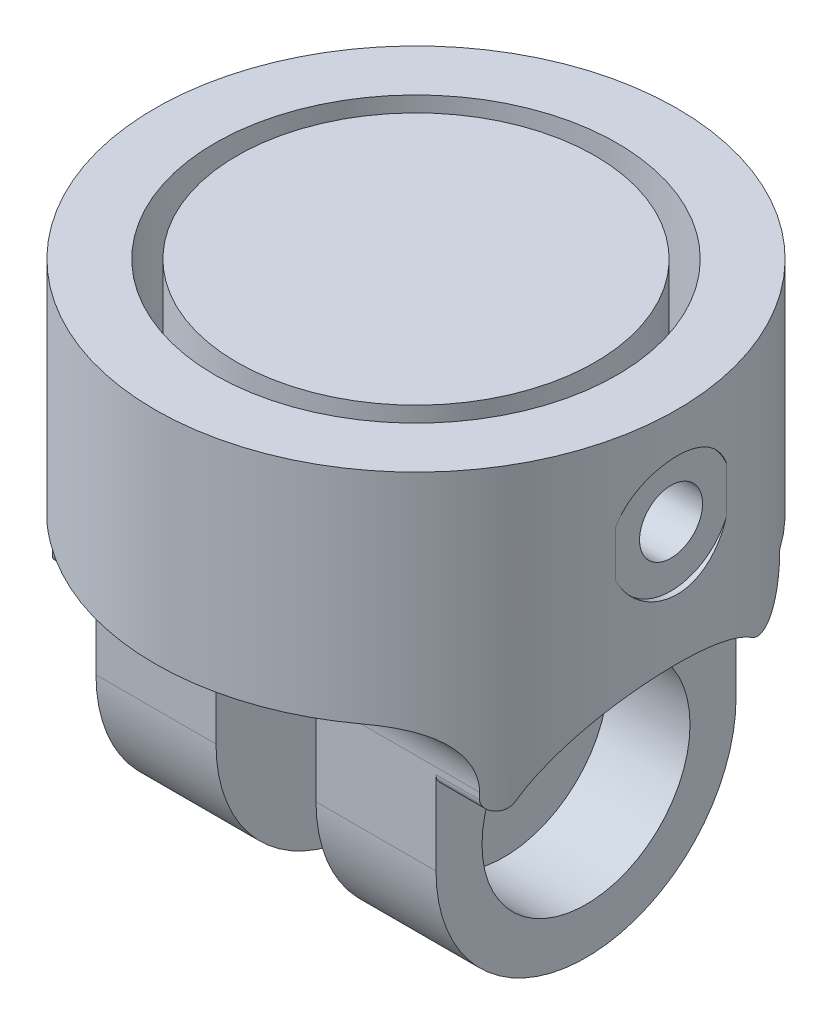
SolidWorks part; units mm, degrees
material "PLA Black"
ref_plane "Front" through (0, 0, 0) normal (0, 0, 1) x (1, 0, 0)
ref_plane "Top" through (0, 0, 0) normal (0, 1, 0) x (1, 0, 0)
ref_plane "Right" through (0, 0, 0) normal (1, 0, 0) x (0, 0, -1)
sketch "Sketch1" plane through (0, 0, 0) normal (0, 1, 0) x (1, 0, 0)
  line L0 (0, 8.95) -> (0, 10.05) construction
  circle A0 centre (0, 0) radius 10.05
  circle A1 centre (0, 0) radius 13.05
  circle A2 centre (0, 0) radius 9.5 construction
  circle A4 centre (0, 0) radius 8.95
  point P11 (0, 9.5)
  dimension "D1" = 1.1
  dimension "D2" = 3
  dimension "D3" = 19
extrude "Boss-Extrude1" add sketch "Sketch1" along normal blind 10 contours A1 A0 | A4 region at (-12.6809, 0, 0) region at (0, 0, 0)
sketch "Sketch3" plane through (0, 0, 0) normal (0, -1, 0) x (1, 0, 0)
  circle A2 centre (0, 0) radius 13.05 construction
  circle A3 centre (0, 0) radius 13.05
extrude "Boss-Extrude2" add sketch "Sketch3" along normal blind 1
sketch "Sketch4" plane through (0, -1, 0) normal (0, -1, 0) x (1, 0, 0)
  line L0 (0, 17.8908) -> (0, -17.0763) construction
  line L1 (2.5, 7.5) -> (8.5, 7.5)
  line L2 (2.5, 7.5) -> (2.5, -7.5)
  line L3 (2.5, -7.5) -> (8.5, -7.5)
  line L4 (8.5, 7.5) -> (8.5, -7.5)
  line L5 (-8.5, 7.5) -> (-8.5, -7.5)
  line L6 (-2.5, -7.5) -> (-8.5, -7.5)
  line L7 (-2.5, 7.5) -> (-2.5, -7.5)
  line L8 (-2.5, 7.5) -> (-8.5, 7.5)
  line L9 (16.8049, 0) -> (-19.8998, 0) construction
  dimension "D1" = 6
  dimension "D2" = 5
  dimension "D3" = 15
extrude "Boss-Extrude3" add sketch "Sketch4" along normal blind 15
sketch "Sketch5" plane through (8.5, 0, 0) normal (1, 0, 0) x (0, 0, -1)
  line L0 (-7.5, -16) -> (-7.5, -1) construction
  line L1 (7.5, -16) -> (7.5, -1) construction
  line L2 (7.5, -8.5) -> (7.5, -17.1619)
  line L3 (7.5, -17.1619) -> (-7.5, -17.1619)
  line L4 (-7.5, -17.1619) -> (-7.5, -8.5)
  arc A0 (-7.5, -8.5) -> (7.5, -8.5) centre (0, -8.5) ccw
  circle A1 centre (0, -8.5) radius 1.55
  dimension "D1" = 3.1
extrude "Cut-Extrude1" cut sketch "Sketch5" against normal through all both and the other way through all
sketch "Sketch6" plane through (8.5, 0, 0) normal (1, 0, 0) x (0, 0, -1)
  circle A0 centre (0, -8.5) radius 5.2
  dimension "D1" = 10.4
extrude "Cut-Extrude2" cut sketch "Sketch6" against normal blind 4.1
mirror "Mirror1" about plane through (0, 0, 0) normal (1, 0, 0) of "Cut-Extrude2"
ref_plane "Plane9" through (1.335, 0, 0) normal (1, 0, 0) x (0, 0, -1)
sketch "Sketch7" plane through (1.335, 0, 0) normal (1, 0, 0) x (0, 0, -1)
  line L0 (3.555, -8.5) -> (3.555, -1) construction
  line L1 (7.5, -1) -> (-7.5, -1) construction
  line L2 (3.4474, -7.632) -> (1.7775, -1) construction
  line L3 (3.1303, -6.8149) -> (0, -1) construction
  line L4 (1.7775, -0.6757) -> (1.7775, -1.4422) construction
  line L5 (2.6911, -6.1771) -> (-1.7775, -1) construction
  line L6 (2.2506, -5.7481) -> (-3.555, -1) construction
  line L8 (0, -1.6788) -> (0, 0) construction
  line L9 (-8.4824, -8.5) -> (8.712, -8.5) construction
  line L10 (1.8766, -5.4807) -> (-5.3325, -1) construction
  line L11 (-3.555, -0.3587) -> (-3.555, -1.6788) construction
  circle A0 centre (0, -8.5) radius 3.555 construction
  dimension "D1" = 7.11
  dimension "D2" = 31.862
  dimension "D3" = 7.5
ref_plane "Plane1" through (1.335, -1, -3.555) normal (0, 1, 0) x (1, 0, 0)
ref_plane "Plane2" through (1.335, -1, -1.7775) normal (0, 0.9697, 0.2442) x (1, 0, 0)
ref_plane "Plane3" through (1.335, -1, 0) normal (0, 0.8805, 0.474) x (1, 0, 0)
ref_plane "Plane5" through (1.335, -1, 1.7775) normal (0, 0.757, 0.6534) x (1, 0, 0)
ref_plane "Plane6" through (1.335, -1, 3.555) normal (0, 0.6331, 0.7741) x (1, 0, 0)
ref_plane "Plane7" through (1.335, -1, 5.3325) normal (0, 0.5279, 0.8493) x (1, 0, 0)
sketch "Sketch8" plane through (1.335, -1, -3.555) normal (0, 1, 0) x (1, 0, 0)
  circle A0 centre (0, 0) radius 0.4895
  dimension "D1" = 0.979
extrude "Cut-Extrude5" cut sketch "Sketch8" along normal blind 5.5 and the other way through all
sketch "Sketch9" plane through (1.335, -1, -1.7775) normal (0, 0.9697, 0.2442) x (1, 0, 0)
  circle A0 centre (0, 0) radius 0.4895
  dimension "D1" = 0.979
extrude "Cut-Extrude3" cut sketch "Sketch9" along normal blind 5.5
sketch "Sketch10" plane through (1.335, -1, 0) normal (0, 0.8805, 0.474) x (1, 0, 0)
  circle A0 centre (0, 0) radius 0.4895
  dimension "D1" = 0.979
sketch "Sketch11" plane through (1.335, -1, 1.7775) normal (0, 0.757, 0.6534) x (1, 0, 0)
  circle A0 centre (0, 0) radius 0.4895
  dimension "D1" = 0.979
sketch "Sketch12" plane through (1.335, -1, 3.555) normal (0, 0.6331, 0.7741) x (1, 0, 0)
  circle A0 centre (0, 0) radius 0.4895
  dimension "D1" = 0.979
sketch "Sketch14" plane through (1.335, -1, 5.3325) normal (0, 0.5279, 0.8493) x (1, 0, 0)
  circle A0 centre (0, 0) radius 0.4895
  dimension "D1" = 0.979
extrude "Cut-Extrude6" cut sketch "Sketch10" along normal blind 5.5 and the other way through all
extrude "Cut-Extrude7" cut sketch "Sketch11" along normal blind 5.5 and the other way through all contours A0
extrude "Cut-Extrude8" cut sketch "Sketch12" along normal blind 5.5 and the other way through all contours A0
extrude "Cut-Extrude9" cut sketch "Sketch14" along normal blind 5.5 and the other way through all contours A0
ref_plane "Plane8" through (13.05, 0, 0) normal (1, 0, 0) x (0, 0, -1)
hole_wizard "Tap Drill for M3 Helicoil1" positions "Sketch17" profile "Sketch18" hole size "M3x0.5" standard "DIN"
sketch "Sketch17" plane through (13.05, 0, 0) normal (1, 0, 0) x (0, 0, -1)
  line L0 (-22.2973, 5) -> (18.0703, 5) construction
  line L4 (0, 12.2732) -> (0, -5.3405) construction
  line L6 (-7.5, -8.5) -> (-7.5, -1) construction
  line L7 (7.5, -8.5) -> (7.5, -1) construction
  line L8 (13.05, 10) -> (-13.05, 10) construction
  line L9 (10.05, 0) -> (-10.05, 0) construction
  point P0 (0, 5)
sketch "Sketch18" plane through (13.05, 5, 0) normal (0, 1, 0) x (0, 0, -1)
  line L0 (0, 0) -> (0, 6.9464)
  line L1 (0, 6.9464) -> (1.575, 6)
  line L2 (1.575, 6) -> (1.575, 0)
  line L5 (1.575, 0) -> (0, 0)
  line L10 (0, 6.9464) -> (-1.575, 6) construction
  line L11 (0, -6.35) -> (0, 107.95) construction
  dimension "Hole Dia." = 3.15
  dimension "Hole Depth" = 6
  dimension "Drill Angle" = 118
sketch "Sketch20" plane through (13.05, 0, 0) normal (1, 0, 0) x (0, 0, -1)
  circle A0 centre (0, 5) radius 3
  dimension "D1" = 6
extrude "Cut-Extrude10" cut sketch "Sketch20" against normal blind 0.3
sketch "Sketch21" plane through (8.5, 0, 0) normal (1, 0, 0) x (0, 0, -1)
  line L0 (7.5, -1) -> (-7.5, -1) construction
  line L1 (7.5, -0.1252) -> (7.5, -1.1767)
  line L2 (0.9244, -19.0662) -> (-4.8209, -14.2453) construction
  line L3 (0, 5.2718) -> (0, -9.2894) construction
  line L4 (0, 10) -> (0, -1) construction
  line L5 (-7.5, -0.1252) -> (-7.5, -4.3226)
  line L6 (7.5, -0.1252) -> (-7.5, -0.1252)
  line L7 (-7.5, -8.5) -> (-7.5, -1) construction
  line L8 (7.5, -8.5) -> (7.5, -1) construction
  line L9 (0, -1) -> (9.4693, -4.4465) construction
  line L10 (0, -1) -> (1.6171, -0.0664) construction
  line L11 (4.6128, -2.5863) -> (7.5, -1.1767) construction
  line L12 (10.5662, -7.5756) -> (4.8209, -2.7547) construction
  line L13 (-4.8209, -14.2453) -> (4.8209, -2.7547) construction
  line L14 (10.5662, -7.5756) -> (0.9244, -19.0662) construction
  arc A0 (-6.4204, -4.6233) -> (4.6128, -2.5863) centre (0, -8.5) cw
  arc A1 (-6.4204, -4.6233) -> (-7.5, -4.3226) centre (-6.9183, -4.3226) cw
  arc A2 (7.5, -1.1767) -> (4.6128, -2.5863) centre (5.7123, -1.1767) cw
  circle A3 centre (0, -8.5) radius 1.55 construction
  arc A4 (-4.8209, -14.2453) -> (4.8209, -2.7547) centre (0, -8.5) cw construction
  dimension "D1" = 30
  dimension "D3" = 7.5
  dimension "D2" = 50
  dimension "D4" = 15
extrude "Boss-Extrude4" add sketch "Sketch21" along normal up to surface (2.1795 mm away) up to face at (12.895, 5, 0)
mirror "Mirror2" about plane through (0, 0, 0) normal (1, 0, 0) of "Boss-Extrude4", "Tap Drill for M3 Helicoil1", "Cut-Extrude10"
fillet "Fillet1" radius 3 2 edges at (-6.5898, -1, 7.5) (6.5898, -1, 7.5)
equation "\"knee_angle\"= 50"
equation "\"ankle_angle\" = 90"
equation "\"hip_angle\" = 30"
equation "\"spring_ankle_parallel_arm_diameter\"= 0.89"
equation "\"spring_ankle_parallel_arm_length\"= 13"
equation "\"spring_ankle_parallel_intern_diameter\"= 6.22"
equation "\"spring_ankle_parallel_angle\"= \"ankle_angle\""
equation "\"spring_ankle_parallel_turns\"= 3"
equation "\"spring_ankle_parallel_pitch\"= \"spring_ankle_parallel_arm_diameter\" * 1.01"
equation "\"spring_ankle_parallel_cutting_distance\"= (1-\"spring_ankle_parallel_angle\" / 360) * \"spring_ankle_parallel_pitch\""
equation "\"spring_ankle_serial_arm_diameter\"= 0.89"
equation "\"spring_ankle_serial_arm_length\"= 10"
equation "\"spring_ankle_serial_intern_diameter\"= 6.22"
equation "\"spring_ankle_serial_angle\"= \"90\""
equation "\"spring_ankle_serial_turns\"= 3"
equation "\"spring_ankle_serial_pitch\"= \"spring_ankle_serial_arm_diameter\" * 1.01"
equation "\"spring_ankle_serial_cutting_distance\"= (1-\"spring_ankle_serial_angle\" / 360) * \"spring_ankle_serial_pitch\""
equation "\"spring_knee_parallel_arm_diameter\"= 0.89"
equation "\"spring_knee_parallel_arm_length\"= 15"
equation "\"spring_knee_parallel_intern_diameter\"= 5.46"
equation "\"spring_knee_parallel_angle\"= -\"knee_angle\" + 90"
equation "\"spring_knee_parallel_turns\"= 3"
equation "\"spring_knee_parallel_pitch\"= \"spring_knee_parallel_arm_diameter\" * 1.01"
equation "\"spring_knee_parallel_cutting_distance\"= (1-(\"spring_knee_parallel_angle\") / 360) * \"spring_knee_parallel_pitch\""
equation "\"spring_knee_serial_arm_diameter\"= 0.89"
equation "\"spring_knee_serial_arm_length\"= 10"
equation "\"spring_knee_serial_intern_diameter\"= 5.46"
equation "\"spring_knee_serial_angle\"= \"90\""
equation "\"spring_knee_serial_turns\"= 3"
equation "\"spring_knee_serial_pitch\"= \"spring_knee_serial_arm_diameter\" * 1.01"
equation "\"spring_knee_serial_cutting_distance\"= (1-\"spring_knee_serial_angle\" / 360) * \"spring_knee_serial_pitch\""
equation "\"spring_ankle_parallel_nominal_diameter\"= \"spring_ankle_parallel_arm_diameter\" + \"spring_ankle_parallel_intern_diameter\""
equation "\"spring_ankle_serial_nominal_diameter\"= \"spring_ankle_serial_arm_diameter\" + \"spring_ankle_serial_intern_diameter\""
equation "\"spring_knee_parallel_nominal_diameter\"= \"spring_knee_parallel_arm_diameter\" + \"spring_knee_parallel_intern_diameter\""
equation "\"spring_knee_serial_nominal_diameter\"= \"spring_knee_serial_arm_diameter\" + \"spring_knee_serial_intern_diameter\""
equation "\"D1@Sketch7\"=\"spring_ankle_parallel_nominal_diameter\""
equation "\"D1@Sketch8\"=\"spring_ankle_parallel_arm_diameter\"*1.1"
equation "\"D1@Sketch9\"=\"spring_ankle_parallel_arm_diameter\"*1.1"
equation "\"D1@Sketch10\"=\"spring_ankle_parallel_arm_diameter\"*1.1"
equation "\"D1@Sketch11\"=\"spring_ankle_parallel_arm_diameter\"*1.1"
equation "\"D1@Sketch12\"=\"spring_ankle_parallel_arm_diameter\"*1.1"
equation "\"D1@Sketch14\"=\"spring_ankle_parallel_arm_diameter\"*1.1"
equation "\"D1@Cut-Extrude3\"=\"spring_ankle_parallel_arm_length\"-\"axis_structure_distance\""
equation "\"axis_structure_distance\"= 7.5"
equation "\"D1@Cut-Extrude5\"=\"spring_ankle_parallel_arm_length\"-\"axis_structure_distance\""
equation "\"D1@Cut-Extrude6\"=\"spring_ankle_parallel_arm_length\"-\"axis_structure_distance\""
equation "\"D1@Cut-Extrude7\"=\"spring_ankle_parallel_arm_length\"-\"axis_structure_distance\""
equation "\"D1@Cut-Extrude8\"=\"spring_ankle_parallel_arm_length\"-\"axis_structure_distance\""
equation "\"D1@Cut-Extrude9\"=\"spring_ankle_parallel_arm_length\"-\"axis_structure_distance\""
equation "\"D1@Boss-Extrude3\"=\"axis_structure_distance\"*2"
equation "\"ankle_angle_max\" = 120"
equation "\"ankle_angle_min\" = 50"
equation "\"knee_angle_max\" = 120"
equation "\"knee_angle_min\" = 0"
equation "\"hip_angle_max\" = 45"
equation "\"hip_angle_min\" = -45"
equation "\"D1@Sketch21\"=\"ankle_angle_max\"-90"
equation "\"D2@Sketch21\"=\"ankle_angle_min\""
equation "\"D1@Plane9\"=(\"spring_ankle_parallel_arm_diameter\"*\"spring_ankle_parallel_turns\")/2"
